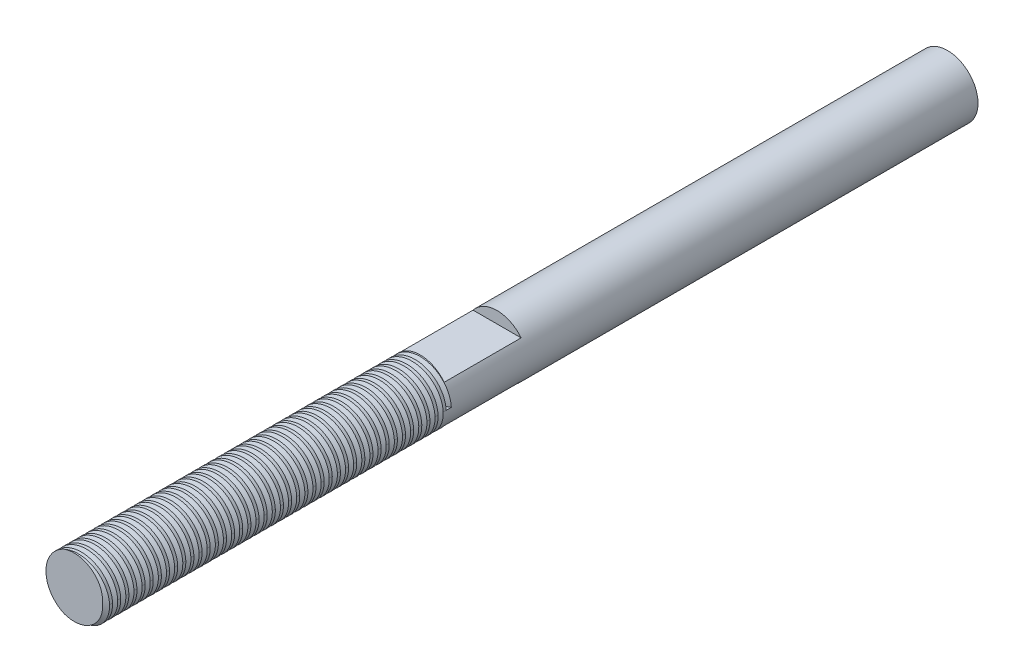
SolidWorks part; units mm, degrees
ref_plane "Front Plane" through (0, 0, 0) normal (0, 0, 1) x (1, 0, 0)
ref_plane "Top Plane" through (0, 0, 0) normal (0, 1, 0) x (1, 0, 0)
ref_plane "Right Plane" through (0, 0, 0) normal (1, 0, 0) x (0, 0, -1)
sketch "Sketch1" plane through (0, 0, 0) normal (0, 0, 1) x (1, 0, 0)
  circle A0 centre (0, 0) radius 3.9688
  dimension "D1" = 7.9375
extrude "Boss-Extrude1" add sketch "Sketch1" along normal blind 113.284
ref_plane "Plane1" through (0, 0, 68.58) normal (0, 0, 1) x (1, 0, 0)
sketch "Sketch2" plane through (0, 0, 68.58) normal (0, 0, 1) x (1, 0, 0)
  line L0 (-3.1256, 2.4457) -> (3.1256, 2.4457)
  line L1 (-3.5581, 0) -> (5.8417, 0) construction
  line L2 (-3.1256, -2.4457) -> (3.1256, -2.4457)
  arc A0 (-3.1256, 2.4457) -> (3.1256, 2.4457) centre (0, 0) cw
  circle A1 centre (0, 0) radius 3.9688 construction
  arc A2 (-3.1256, -2.4457) -> (3.1256, -2.4457) centre (0, 0) ccw
extrude "Cut-Extrude1" cut sketch "Sketch2" against normal blind 10
sketch "Sketch3" plane through (0, 0, 113.284) normal (0, 0, 1) x (1, 0, 0)
  circle A0 centre (0, 0) radius 3.9688 construction
  circle A1 centre (0, 0) radius 3.9688
curve "Helix/Spiral1" pitch 1.0583 height 44.45 radius 3.9688 centre (0, 0, 113.284) axis (0, 0, -1) start towards (1, 0, 0)
sketch "Sketch7" plane through (0, 0, 0) normal (0, 1, 0) x (1, 0, 0)
  line L1 (3.3914, -113.284) -> (4.2574, -113.784)
  line L2 (4.2574, -113.784) -> (4.2574, -112.784)
  line L3 (4.2574, -112.784) -> (3.3914, -113.284)
  circle A0 centre (3.9688, -113.284) radius 0.2887 construction
  dimension "D1" = 1
sweep "Cut-Sweep1" cut profiles "Sketch7" path "Helix/Spiral1" align with end faces yes
